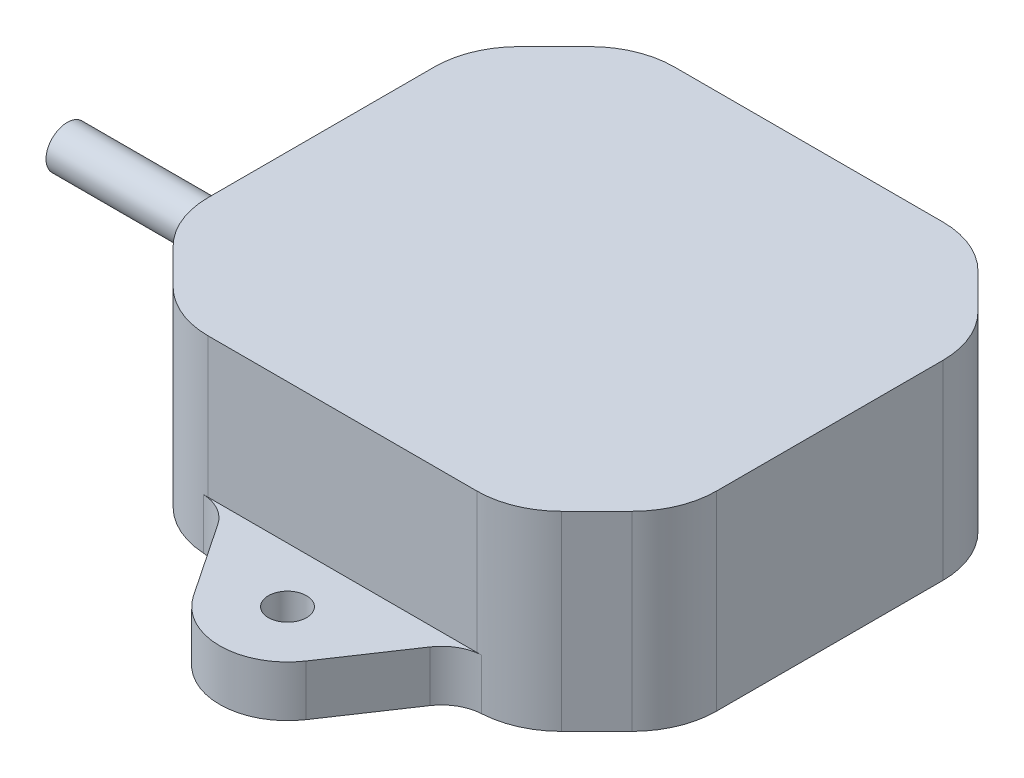
SolidWorks part; units mm, degrees
ref_plane "Front Plane" through (0, 0, 0) normal (0, 0, 1) x (1, 0, 0)
ref_plane "Top Plane" through (0, 0, 0) normal (0, 1, 0) x (1, 0, 0)
ref_plane "Right Plane" through (0, 0, 0) normal (1, 0, 0) x (0, 0, -1)
sketch "Sketch1" plane through (0, 0, 0) normal (0, 1, 0) x (1, 0, 0)
  line L1 (-30, 27.5) -> (30, 27.5)
  line L2 (-30, 27.5) -> (-30, -27.5)
  line L3 (-30, -27.5) -> (30, -27.5)
  line L4 (30, 27.5) -> (30, -27.5)
  line L5 (-30, 27.5) -> (30, -27.5) construction
  line L6 (-30, -27.5) -> (30, 27.5) construction
  point P0 (0, 0)
  dimension "D1" = 60
  dimension "D2" = 55
extrude "Boss-Extrude1" add sketch "Sketch1" along normal mid plane 22.5 contours L1 L4 L3 L2
sketch "Sketch2" plane through (0, -11.25, 0) normal (0, -1, 0) x (1, 0, 0)
  line L0 (-14, -27.5) -> (-6.6418, -38.4594)
  line L1 (-30, -27.5) -> (30, -27.5) construction
  line L2 (-14, -27.5) -> (14, -27.5)
  line L3 (6.6418, -38.4594) -> (14, -27.5)
  line L4 (-30, -27.5) -> (-30, 27.5) construction
  arc A0 (-6.6418, -38.4594) -> (6.6418, -38.4594) centre (0, -34) ccw
  circle A1 centre (0, -34) radius 2.25
  point P10 (0, -42)
  dimension "D3" = 4.5
  dimension "D1" = 42
  dimension "D2" = 16
  dimension "D4" = 34
extrude "Boss-Extrude2" add sketch "Sketch2" against normal blind 6
mirror "Mirror1" about plane through (0, 0, 0) normal (0, 0, 1) of "Boss-Extrude2"
chamfer "Chamfer1" distance 10 angle 45 4 edges at (-30, 0, 27.5) (30, 0, 27.5) (30, 0, -27.5) (-30, 0, -27.5)
fillet "Fillet1" radius 10 8 edges at (30, 0, -17.5) (20, 0, -27.5) (-20, 0, -27.5) (-30, 0, -17.5) (-30, 0, 17.5) (-20, 0, 27.5) (30, 0, 17.5) (20, 0, 27.5)
fillet "Fillet2" radius 5 4 edges at (14, -8.25, -27.5) (-14, -8.25, -27.5) (-14, -8.25, 27.5) (14, -8.25, 27.5)
sketch "Sketch3" plane through (-30, 0, 0) normal (-1, 0, 0) x (0, 0, 1)
  line L0 (29.6903, -5.25) -> (38.4594, -5.25) construction
  circle A0 centre (0, -5.25) radius 2.5
  dimension "D1" = 5
extrude "Boss-Extrude3" add sketch "Sketch3" along normal blind 30
